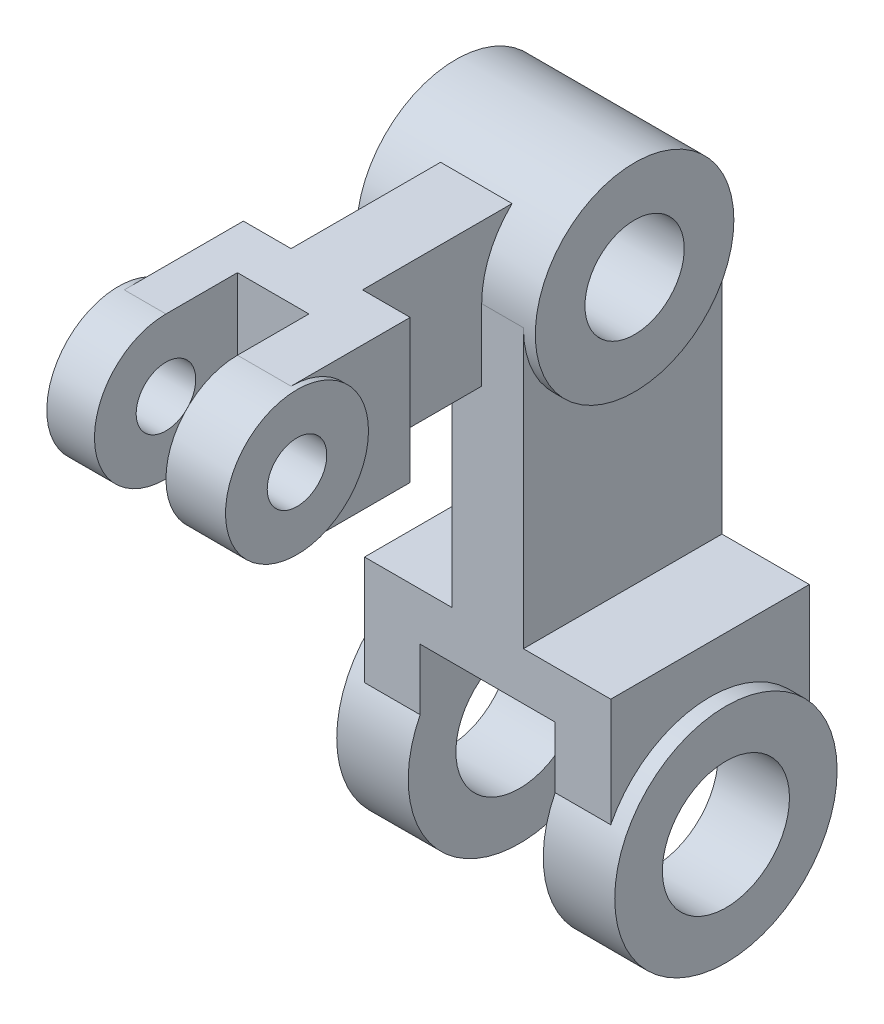
SolidWorks part; units mm, degrees
ref_plane "Plan de face" through (0, 0, 0) normal (0, 0, 1) x (1, 0, 0)
ref_plane "Plan de dessus" through (0, 0, 0) normal (0, 1, 0) x (1, 0, 0)
ref_plane "Plan de droite" through (0, 0, 0) normal (1, 0, 0) x (0, 0, -1)
sketch "Esquisse1" plane through (0, 0, 0) normal (1, 0, 0) x (0, 0, -1)
  circle A0 centre (0, 0) radius 18
  circle A1 centre (85, 0) radius 25
  circle A2 centre (0, 0) radius 7.5
  circle A3 centre (85, 0) radius 12.5
  dimension "D1" = 36
  dimension "D2" = 15
  dimension "D3" = 50
  dimension "D4" = 25
  dimension "D5" = 85
extrude "Boss.-Extru.1" add sketch "Esquisse1" along normal blind 45
sketch "Esquisse3" plane through (45, 0, 0) normal (1, 0, 0) x (0, 0, -1)
  line L0 (60, 0) -> (60, -70)
  line L1 (60, -70) -> (110, -70)
  line L2 (110, -70) -> (110, 0)
  circle A0 centre (85, 0) radius 25 construction
  arc A1 (60, 0) -> (110, 0) centre (85, 0) ccw
  dimension "D1" = 70
extrude "Boss.-Extru.2" add sketch "Esquisse3" against normal blind 18 from offset 3 offset against normal yes
ref_plane "Plan1" through (33, 0, 0) normal (1, 0, 0) x (0, 0, -1)
sketch "Esquisse4" plane through (33, 0, 0) normal (1, 0, 0) x (0, 0, -1)
  circle A0 centre (85, -110) radius 28
  circle A1 centre (85, -110) radius 16
  dimension "D1" = 56
  dimension "D2" = 32
  dimension "D3" = 110
extrude "Boss.-Extru.3" add sketch "Esquisse4" against normal mid plane 70 separate body
sketch "Esquisse5" plane through (33, 0, 0) normal (1, 0, 0) x (0, 0, -1)
  line L0 (60, -70) -> (60, -97.3905)
  line L1 (110, -70) -> (110, -97.3905)
  line L2 (110, -70) -> (60, -70)
  circle A0 centre (85, -110) radius 28 construction
  arc A1 (110, -97.3905) -> (60, -97.3905) centre (85, -110) ccw
extrude "Boss.-Extru.4" add sketch "Esquisse5" along normal mid plane 62
sketch "Esquisse6" plane through (0, 0, -110) normal (0, 0, -1) x (-1, 0, 0)
  line L0 (-68, -138) -> (2, -138) construction
  line L1 (-50, -82) -> (-16, -82)
  line L2 (-50, -82) -> (-50, -138)
  line L3 (-50, -138) -> (-16, -138)
  line L4 (-16, -82) -> (-16, -138)
  line L5 (-50, -82) -> (-16, -138) construction
  line L6 (-50, -138) -> (-16, -82) construction
  line L7 (2, -138) -> (2, -82) construction
  line L8 (-24, -70) -> (-2, -70) construction
  point P0 (-33, -110)
  dimension "D1" = 34
  dimension "D2" = 18
  dimension "D3" = 12
extrude "Enlèv. mat.-Extru.1" cut sketch "Esquisse6" against normal through all both and the other way through all
ref_plane "Plan2" through (22.5, 0, 0) normal (-1, 0, 0) x (0, 0, 1)
sketch "Esquisse7" plane through (22.5, 0, 0) normal (-1, 0, 0) x (0, 0, 1)
  line L0 (0, 18) -> (-67.6506, 18)
  line L1 (0, -18) -> (-67.6506, -18)
  line L2 (-30, 18) -> (-30, -18)
  circle A0 centre (0, 0) radius 18 construction
  circle A1 centre (-85, 0) radius 25 construction
  arc A2 (-110, 0) -> (-60, 0) centre (-85, 0) ccw construction
  circle A3 centre (-85, 0) radius 12.5 construction
  arc A4 (0, 18) -> (0, -18) centre (0, 0) ccw
  arc A5 (-67.6506, -18) -> (-67.6506, 18) centre (-85, 0) ccw
  point P15 (0, 0)
  dimension "D1" = 55
  dimension "D2" = 36
extrude "Boss.-Extru.5" add sketch "Esquisse7" along normal mid plane 42 contours A4 L0 L2 L1 region at (22.5, 0, -21.5598)
extrude "Boss.-Extru.6" add sketch "Esquisse7<4>" along normal mid plane 18 contours A5 L1 L2 L0 region at (22.5, 0, -46.2609)
sketch "Esquisse7<4>" plane through (22.5, 0, 0) normal (-1, 0, 0) x (0, 0, 1) same geometry as "Esquisse7"
sketch "Esquisse10" plane through (0, 18, 0) normal (0, 1, 0) x (1, 0, 0)
  line L0 (0, -18) -> (45, -18) construction
  line L1 (12, -18) -> (30, -18)
  line L2 (12, -18) -> (12, 18)
  line L3 (12, 18) -> (30, 18)
  line L4 (30, -18) -> (30, 18)
  line L5 (1.5, 30) -> (13.5, 30) construction
  line L6 (0, 18) -> (0, -18) construction
  line L7 (45, -18) -> (45, 18) construction
  dimension "D1" = 12
  dimension "D2" = 12
  dimension "D3" = 18
extrude "Enlèv. mat.-Extru.2" cut sketch "Esquisse10" against normal through all
